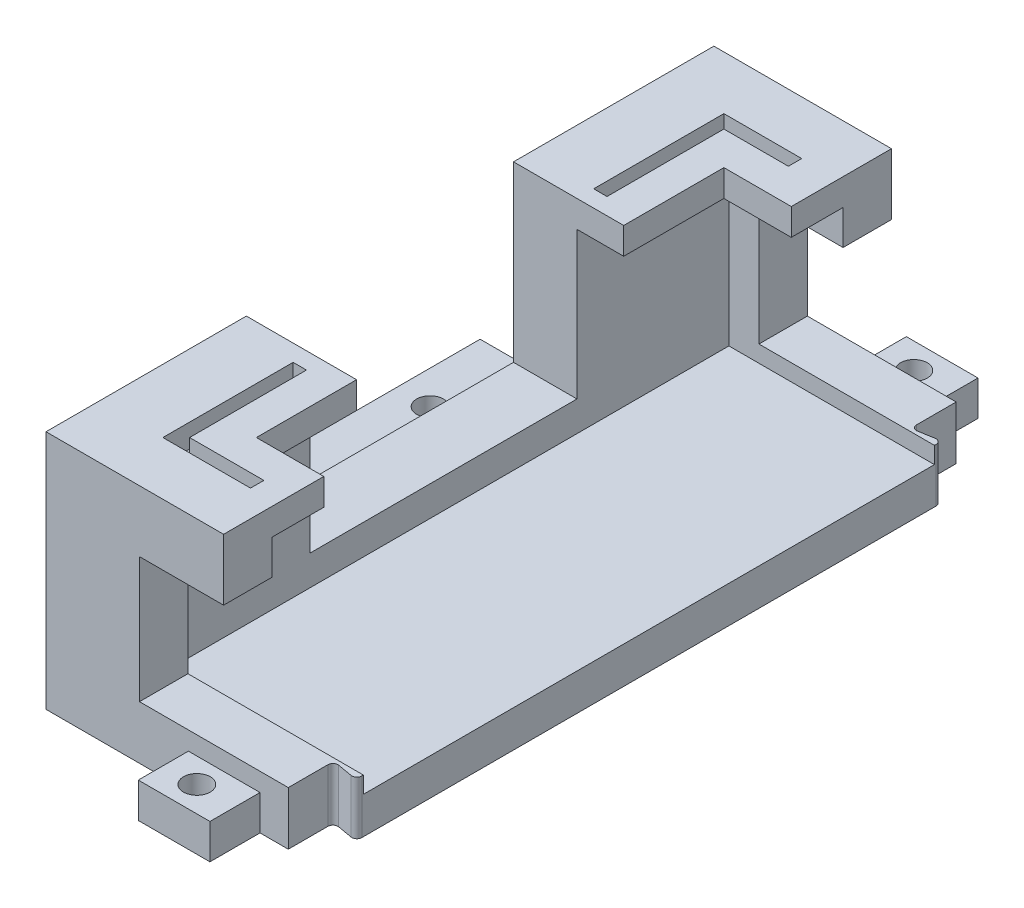
SolidWorks part; units mm, degrees
ref_plane "Front Plane" through (0, 0, 0) normal (0, 0, 1) x (1, 0, 0)
ref_plane "Top Plane" through (0, 0, 0) normal (0, 1, 0) x (1, 0, 0)
ref_plane "Right Plane" through (0, 0, 0) normal (1, 0, 0) x (0, 0, -1)
sketch "Sketch1" plane through (0, 0, 0) normal (0, 1, 0) x (1, 0, 0)
  line L1 (-184.5, -100) -> (184.5, -100)
  line L2 (-184.5, -100) -> (-184.5, 100)
  line L3 (-184.5, 100) -> (184.5, 100)
  line L4 (184.5, -100) -> (184.5, 100)
  line L5 (-184.5, -100) -> (184.5, 100) construction
  line L6 (-184.5, 100) -> (184.5, -100) construction
  point P0 (0, 0)
  dimension "D1" = 200
  dimension "353" = 369
extrude "Boss-Extrude1" add sketch "Sketch1" along normal blind 20
sketch "Sketch2" plane through (0, 20, 0) normal (0, 1, 0) x (1, 0, 0)
  line L0 (-184.5, -100) -> (184.5, -100) construction
  line L1 (-184.5, -100) -> (-151.6166, -100)
  line L2 (-184.5, -100) -> (-184.5, -36.5)
  line L3 (-184.5, -36.5) -> (-165.5, -36.5)
  line L4 (-165.5, -84) -> (-165.5, -36.5)
  line L5 (-184.5, 100) -> (-151.6166, 100)
  line L6 (-184.5, 100) -> (-184.5, 36.5)
  line L7 (-184.5, 36.5) -> (-165.5, 36.5)
  line L8 (-165.5, 84) -> (-165.5, 36.5)
  line L9 (-151.6166, 100) -> (-115.5, 100)
  line L11 (-165.5, 84) -> (-115.5, 84)
  line L12 (-115.5, 100) -> (-115.5, 84)
  line L13 (-151.6166, -100) -> (-115.5, -100)
  line L15 (-165.5, -84) -> (-115.5, -84)
  line L16 (-115.5, -100) -> (-115.5, -84)
  line L17 (-40.5, -100) -> (84.5, -100)
  line L18 (-40.5, -100) -> (-40.5, -84)
  line L19 (-40.5, -84) -> (84.5, -84)
  line L20 (84.5, -100) -> (84.5, -84)
  line L21 (184.5, 100) -> (-184.5, 100) construction
  line L22 (-40.5, 100) -> (84.5, 100)
  line L23 (-40.5, 100) -> (-40.5, 84)
  line L24 (-40.5, 84) -> (84.5, 84)
  line L25 (84.5, 100) -> (84.5, 84)
  line L26 (184.5, -100) -> (184.5, 100) construction
  line L27 (-184.5, 100) -> (-184.5, -100) construction
  point P28 (84.5, -92)
  dimension "D1" = 65
  dimension "D2" = 19
  dimension "D3" = 65
  dimension "D4" = 19
  dimension "D5" = 16
  dimension "D6" = 50
  dimension "D7" = 50
  dimension "D8" = 16
  dimension "D9" = 75
  dimension "D10" = 100
extrude "Boss-Extrude2" add sketch "Sketch2" along normal blind 12
sketch "Sketch3" plane through (0, 20, 0) normal (0, 1, 0) x (1, 0, 0)
  line L0 (-115.5, -84) -> (-165.5, -84) construction
  line L1 (-165.5, 84) -> (176.5, 84)
  line L2 (-165.5, 84) -> (-165.5, -84)
  line L3 (-165.5, -84) -> (176.5, -84)
  line L4 (176.5, 84) -> (176.5, -84)
  dimension "D1" = 342
extrude "Cut-Extrude1" cut sketch "Sketch3" against normal blind 9
sketch "Sketch4" plane through (0, 0, -100) normal (0, 0, -1) x (-1, 0, 0)
  line L0 (-84.5, 32) -> (40.5, 32) construction
  line L1 (-69.5, 20) -> (30.5, 20)
  line L2 (-69.5, 20) -> (-69.5, 32)
  line L3 (-69.5, 32) -> (30.5, 32)
  line L4 (30.5, 20) -> (30.5, 32)
  line L5 (-69.5, 20) -> (30.5, 32) construction
  line L6 (-69.5, 32) -> (30.5, 20) construction
  line L8 (-84.5, 32) -> (-84.5, 20) construction
  point P0 (-19.5, 26)
  dimension "D1" = 100
  dimension "D2" = 15
extrude "Boss-Extrude3" add sketch "Sketch4" along normal blind 60
sketch "Sketch6" plane through (0, 0, -84) normal (0, 0, 1) x (1, 0, 0)
  line L0 (-20.5, 32) -> (-22.7871, 29.1015)
  line L1 (-40.5, 32) -> (84.5, 32) construction
  line L2 (-21.3663, 26.1706) -> (-11.6337, 26.1706)
  line L3 (-10.2129, 29.1015) -> (-12.5, 32)
  line L4 (-12.5, 32) -> (-20.5, 32)
  line L5 (-40.5, 32) -> (84.5, 32) construction
  line L6 (-40.5, 32) -> (-40.5, 20) construction
  line L7 (56.5, 32) -> (54.2501, 28.6971)
  line L8 (55.6337, 26.0806) -> (65.3663, 26.0806)
  line L9 (66.7499, 28.6971) -> (64.5, 32)
  line L10 (64.5, 32) -> (56.5, 32)
  line L12 (84.5, 32) -> (84.5, 20) construction
  arc A0 (-22.7871, 29.1015) -> (-21.3663, 26.1706) centre (-21.3663, 27.9804) ccw
  arc A1 (-11.6337, 26.1706) -> (-10.2129, 29.1015) centre (-11.6337, 27.9804) ccw
  arc A2 (54.2501, 28.6971) -> (55.6337, 26.0806) centre (55.6337, 27.7546) ccw
  arc A3 (65.3663, 26.0806) -> (66.7499, 28.6971) centre (65.3663, 27.7546) ccw
  dimension "D1" = 8
  dimension "D2" = 20
  dimension "D3" = 8
  dimension "D4" = 20
extrude "Cut-Extrude3" cut sketch "Sketch6" against normal blind 60 and the other way blind 10
sketch "Sketch8" plane through (0, 32, 0) normal (0, 1, 0) x (1, 0, 0)
  line L0 (-184.5, 36.5) -> (-165.5, 36.5)
  line L1 (-165.5, 36.5) -> (-165.5, 84)
  line L2 (-165.5, 84) -> (-115.5, 84)
  line L3 (-115.5, 84) -> (-115.5, 100)
  line L4 (-115.5, 100) -> (-184.5, 100)
  line L5 (-184.5, 100) -> (-184.5, 36.5)
extrude "Boss-Extrude5" add sketch "Sketch8" along normal blind 40
sketch "Sketch9" plane through (0, 72, 0) normal (0, 1, 0) x (1, 0, 0)
  line L0 (-115.5, 84) -> (-115.5, 70)
  line L1 (-115.5, 70) -> (-151.5, 70)
  line L2 (-151.5, 70) -> (-151.5, 35)
  line L3 (-151.5, 35) -> (-165.5, 35)
  line L4 (-165.5, 36.5) -> (-165.5, 84) construction
  line L5 (-165.5, 84) -> (-165.5, -84) construction
  line L6 (176.5, 84) -> (-165.5, 84) construction
  dimension "D1" = 14
  dimension "D2" = 14
extrude "Extrude-Thin1" add sketch "Sketch9" against normal blind 7 thin thin type one direction wall 10
mirror "Mirror2" about plane through (0, 0, 0) normal (0, 0, 1) of "Boss-Extrude5", "Boss-Extrude3", "Cut-Extrude3", "Extrude-Thin1"
sketch "Sketch10" plane through (0, 32, 0) normal (0, 1, 0) x (1, 0, 0)
  line L1 (-103.95, 161.5046) -> (300.05, 161.5046)
  line L2 (-103.95, 161.5046) -> (-103.95, -163.2916)
  line L3 (-103.95, -163.2916) -> (300.05, -163.2916)
  line L4 (300.05, 161.5046) -> (300.05, -163.2916)
  line L6 (-184.5, 36.5) -> (-184.5, -36.5) construction
  dimension "D1" = 80.55
  dimension "D2" = 404
extrude "Cut-Extrude4" cut sketch "Sketch10" against normal blind 69
sketch "Sketch14" plane through (0, 0, -100) normal (0, 0, -1) x (-1, 0, 0)
  line L5 (115.5, 72) -> (115.5, 20) construction
  line L6 (115.5, 53.6124) -> (156.5, 53.6124)
  line L7 (115.5, 53.6124) -> (115.5, 18.895)
  line L8 (115.5, 18.895) -> (156.5, 18.895)
  line L9 (156.5, 53.6124) -> (156.5, 18.895)
  line L10 (184.5, 72) -> (184.5, 0) construction
  dimension "D1" = 28
extrude "Cut-Extrude7" cut sketch "Sketch14" against normal through all both and the other way through all
sketch "Sketch11" plane through (0, 20, 0) normal (0, 1, 0) x (1, 0, 0)
  line L2 (-103.95, 96.25) -> (-103.95, 87.75)
  line L5 (-103.95, 96.25) -> (-111.95, 97.6606)
  line L6 (-111.95, 97.6606) -> (-111.95, 86.3394)
  line L7 (-111.95, 86.3394) -> (-103.95, 87.75)
  line L8 (-103.95, -84) -> (-103.95, -100) construction
  line L9 (-103.95, 100) -> (-115.5, 100) construction
  line L11 (-103.95, -87.75) -> (-103.95, -96.25)
  line L15 (-103.95, 84) -> (-103.95, 100) construction
  line L18 (-103.95, -87.75) -> (-111.95, -86.3394)
  line L19 (-111.95, -86.3394) -> (-111.95, -97.6606)
  line L20 (-111.95, -97.6606) -> (-103.95, -96.25)
  line L21 (-103.95, -100) -> (-103.95, -84) construction
  line L22 (-115.5, -100) -> (-103.95, -100) construction
  dimension "D2" = 3.75
  dimension "D3" = 80
  dimension "D4" = 80
  dimension "D5" = 80
  dimension "D6" = 3.75
  dimension "D7" = 3.75
  dimension "D8" = 80
  dimension "D9" = 3.75
  dimension "D10" = 8
  dimension "D11" = 8
sketch "Sketch12" plane through (-184.5, 0, 0) normal (-1, 0, 0) x (0, 0, 1)
  line L1 (0, 0) -> (-50, 0)
  line L2 (0, 0) -> (0, 11)
  line L3 (0, 11) -> (-50, 11)
  line L4 (-50, 0) -> (-50, 11)
  dimension "D1" = 11
  dimension "D2" = 50
extrude "Boss-Extrude6" add sketch "Sketch12" along normal blind 20
sketch "Sketch13" plane through (0, 11, 0) normal (0, 1, 0) x (1, 0, 0)
  line L0 (-204.5, 0) -> (-204.5, 50) construction
  line L1 (-204.5, 50) -> (-184.5, 50) construction
  circle A0 centre (-194.5, 25) radius 4
  dimension "D1" = 10
  dimension "D2" = 25
extrude "Cut-Extrude6" cut sketch "Sketch13" against normal through all
mirror "Mirror3" about plane through (0, 0, 0) normal (0, 0, 1) of "Cut-Extrude6", "Boss-Extrude6"
extrude "Cut-Extrude9" cut sketch "Sketch11" against normal through all
sketch "Sketch16" plane through (0, 0, 100) normal (0, 0, 1) x (1, 0, 0)
  line L0 (-156.5, 53.6124) -> (-115.5, 53.6124) construction
  line L1 (-115.5, 72) -> (-131.3145, 72)
  line L2 (-115.5, 72) -> (-115.5, 53.6124)
  line L3 (-115.5, 53.6124) -> (-131.3145, 53.6124)
  line L4 (-131.3145, 72) -> (-131.3145, 53.6124)
extrude "Cut-Extrude10" cut sketch "Sketch16" against normal through all
sketch "Sketch18" plane through (0, 72, 0) normal (0, 1, 0) x (1, 0, 0)
  line L1 (-131.3145, -70) -> (-139.2597, -70)
  line L2 (-131.3145, -70) -> (-131.3145, -92.041)
  line L3 (-131.3145, -92.041) -> (-139.2597, -92.041)
  line L4 (-139.2597, -70) -> (-139.2597, -92.041)
extrude "Boss-Extrude8" add sketch "Sketch18" against normal up to vertex (7 mm away) up to point (-131.3145, 65, 70)
sketch "Sketch19" plane through (0, 72, 0) normal (0, 1, 0) x (1, 0, 0)
  line L1 (-131.3145, 70) -> (-142.1923, 70)
  line L2 (-131.3145, 70) -> (-131.3145, 90.9542)
  line L3 (-131.3145, 90.9542) -> (-142.1923, 90.9542)
  line L4 (-142.1923, 70) -> (-142.1923, 90.9542)
extrude "Boss-Extrude9" add sketch "Sketch19" against normal up to vertex (7 mm away) up to point (-131.3145, 65, -70)
fillet "Fillet1" radius 1.5 8 edges at (-111.95, 10, -97.6606) (-103.95, 10, -96.25) (-103.95, 10, -87.75) (-111.95, 10, -86.3394) (-103.95, 10, 96.25) (-111.95, 10, 97.6606) (-111.95, 10, 86.3394) (-103.95, 10, 87.75)
sketch "Sketch20" plane through (0, 0, 100) normal (0, 0, 1) x (1, 0, 0)
  line L0 (-156.5, 18.895) -> (-156.5, 53.6124) construction
  line L1 (-146.5, 18.895) -> (-156.5, 18.895)
  line L2 (-146.5, 18.895) -> (-146.5, 15.995)
  line L3 (-146.5, 15.995) -> (-156.5, 15.995)
  line L4 (-156.5, 18.895) -> (-156.5, 15.995)
  dimension "D1" = 2.9
extrude "Cut-Extrude11" cut sketch "Sketch20" against normal through all both and the other way through all
sketch "Sketch21" plane through (-184.5, 0, 0) normal (-1, 0, 0) x (0, 0, 1)
  line L0 (-100, 72) -> (-36.5, 72) construction
  line L1 (-40, 72) -> (-33.1471, 72)
  line L2 (-40, 72) -> (-40, 20)
  line L3 (-40, 20) -> (-33.1471, 20)
  line L4 (-33.1471, 72) -> (-33.1471, 20)
  line L5 (-36.5, 20) -> (36.5, 20) construction
  line L6 (-100, 72) -> (-100, 0) construction
  line L7 (35, 72) -> (40, 72)
  line L8 (35, 72) -> (35, 20)
  line L9 (35, 20) -> (40, 20)
  line L10 (40, 72) -> (40, 20)
  line L11 (100, 72) -> (100, 0) construction
  dimension "D1" = 60
  dimension "D2" = 60
extrude "Cut-Extrude12" cut sketch "Sketch21" against normal through all
sketch "Sketch22" plane through (0, 0, 100) normal (0, 0, 1) x (1, 0, 0)
  line L1 (-146.5, 15.995) -> (-103.3169, 15.995)
  line L2 (-146.5, 15.995) -> (-146.5, 28.4244)
  line L3 (-146.5, 28.4244) -> (-103.3169, 28.4244)
  line L4 (-103.3169, 15.995) -> (-103.3169, 28.4244)
extrude "Cut-Extrude13" cut sketch "Sketch22" against normal through all
sketch "Sketch23" plane through (0, 65, 0) normal (0, -1, 0) x (-1, 0, 0)
  line L0 (161.5, -80) -> (161.5, -45) construction
  line L1 (151.5, -70) -> (131.3145, -70)
  line L3 (156.1731, -84) -> (131.3145, -84)
  line L4 (131.3145, -70) -> (131.3145, -84)
  line L5 (161.5, -73) -> (131.3145, -84) construction
  line L6 (156.1731, -84) -> (131.3145, -70) construction
  line L7 (165.5, -40) -> (165.5, -45) construction
  line L8 (151.5, -40) -> (165.5, -40)
  line L9 (151.5, -40) -> (151.5, -70)
  line L11 (165.5, -40) -> (165.5, -71.5)
  line L15 (156.1731, -84) -> (165.5, -84)
  line L16 (165.5, -71.5) -> (165.5, -84)
  point P0 (146.4072, -78.5)
extrude "Boss-Extrude10" add sketch "Sketch23" along normal blind 1
mirror "Mirror4" about plane through (0, 0, 0) normal (0, 0, 1) of "Boss-Extrude10"
sketch "Sketch24" plane through (-103.95, 0, 0) normal (1, 0, 0) x (0, 0, -1)
  line L0 (-84, 64) -> (-40, 64) construction
  line L1 (-84, 11) -> (-85.5, 11)
  line L2 (-84, 11) -> (-84, 64)
  line L3 (-84, 64) -> (-85.5, 64)
  line L4 (-85.5, 11) -> (-85.5, 64)
  dimension "D1" = 1.5
extrude "Cut-Extrude14" cut sketch "Sketch24" against normal up to surface (61.55 mm away) up to face at (-165.5, 68.5, -64.5)
mirror "Mirror5" about plane through (0, 0, 0) normal (0, 0, 1) of "Cut-Extrude14"
sketch "Sketch25" plane through (0, 0, 100) normal (0, 0, 1) x (1, 0, 0)
  line L0 (-184.5, 0) -> (-103.95, 0) construction
  line L1 (-141.8616, 0) -> (-120.4075, 0)
  line L2 (-141.8616, 0) -> (-141.8616, 10.4853)
  line L3 (-141.8616, 10.4853) -> (-120.4075, 10.4853)
  line L4 (-120.4075, 0) -> (-120.4075, 10.4853)
extrude "Boss-Extrude11" add sketch "Sketch25" along normal blind 15
sketch "Sketch26" plane through (0, 10.4853, 0) normal (0, 1, 0) x (1, 0, 0)
  circle A0 centre (-131.9664, -107.3588) radius 4
  dimension "D1" = 8
extrude "Cut-Extrude15" cut sketch "Sketch26" against normal blind 15
sketch "Sketch27" plane through (0, 15.995, 0) normal (0, 1, 0) x (1, 0, 0)
  line L0 (-111.95, -88.127) -> (-111.95, -95.873) construction
  line L1 (-103.95, -100) -> (-111.95, -100)
  line L2 (-103.95, -100) -> (-103.95, -89.4261)
  line L3 (-103.95, -89.4261) -> (-111.95, -89.4261)
  line L4 (-111.95, -100) -> (-111.95, -89.4261)
extrude "Cut-Extrude16" cut sketch "Sketch27" against normal through all
mirror "Mirror6" about plane through (0, 0, 0) normal (0, 0, 1) of "Cut-Extrude16", "Cut-Extrude15", "Boss-Extrude11"
